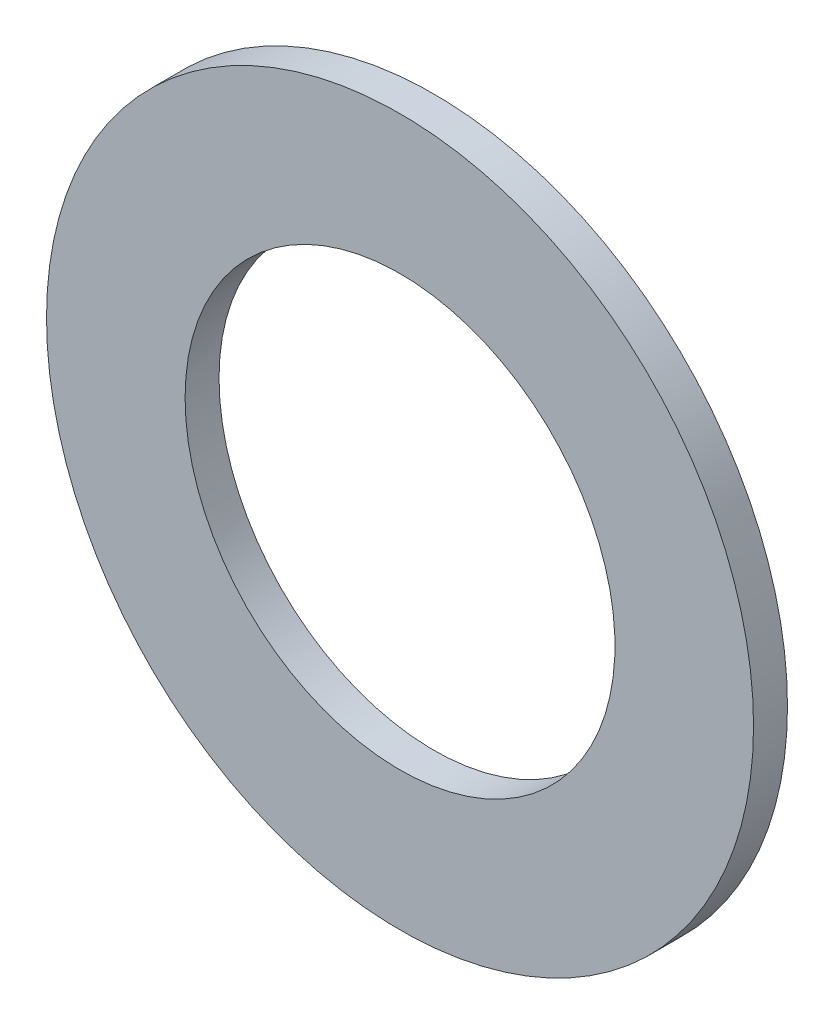
SolidWorks part; units mm, degrees
material "AISI 316 Stainless Steel"
ref_plane "Front Plane" through (0, 0, 0) normal (0, 0, 1) x (1, 0, 0)
ref_plane "Top Plane" through (0, 0, 0) normal (0, 1, 0) x (1, 0, 0)
ref_plane "Right Plane" through (0, 0, 0) normal (1, 0, 0) x (0, 0, -1)
ref_axis "Axis1" through (0, 0, -88.99) along (0, 0, 1)
ref_axis "Axis2" through (0, -55, 0) along (0, 1, 0)
ref_axis "Axis3" through (-88.99, 0, 0) along (1, 0, 0)
sketch "Sketch1" plane through (0, 0, 0) normal (0, 0, 1) x (1, 0, 0)
  circle A0 centre (0, 0) radius 15.875
  circle A1 centre (0, 0) radius 9.652
  dimension "D1" = 19.304
  dimension "D2" = 31.75
extrude "Boss-Extrude1" add sketch "Sketch1" along normal blind 1.524
